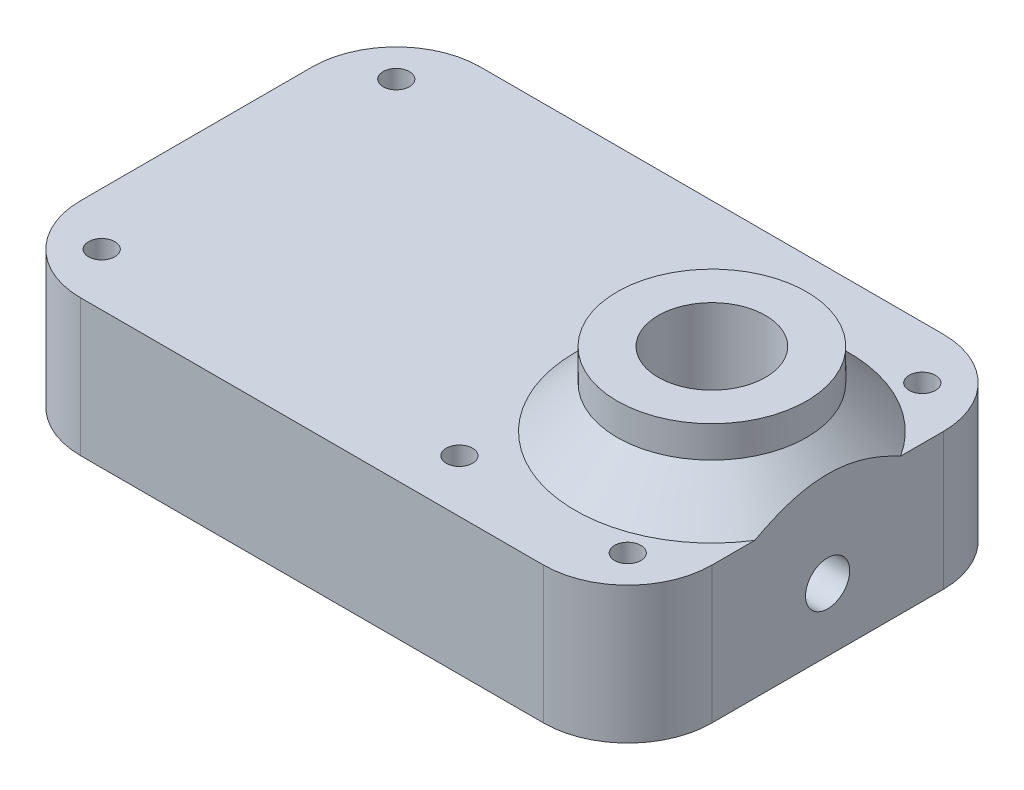
SolidWorks part; units mm, degrees
material "Aluminum 101"
ref_plane "Front Plane" through (0, 0, 0) normal (0, 0, 1) x (1, 0, 0)
ref_plane "Top Plane" through (0, 0, 0) normal (0, 1, 0) x (1, 0, 0)
ref_plane "Right Plane" through (0, 0, 0) normal (1, 0, 0) x (0, 0, -1)
sketch "Sketch1" plane through (0, 0, 0) normal (0, 1, 0) x (1, 0, 0)
  line L1 (-49, 19) -> (11, 19)
  line L2 (-49, 19) -> (-49, -19)
  line L3 (-49, -19) -> (11, -19)
  line L4 (11, 19) -> (11, -19)
  circle A1 centre (0, 0) radius 9
  point P8 (11, 0)
  dimension "D2" = 18
  dimension "D3" = 38
  dimension "D4" = 60
  dimension "D1" = 11
extrude "Base" add sketch "Sketch1" along normal blind 13 contours L4 A1 L1 L2 L3 | A1 region at (-21.387, 0, 0) region at (0, 0, 0)
fillet "AddALittleBeauty" radius 8 4 edges at (-49, 6.5, 19) (-49, 6.5, -19) (11, 6.5, -19) (11, 6.5, 19)
extrude "RodHolder" add sketch "Sketch1<3>" along normal blind 20 contours A1 region at (0, 0, 0)
sketch "Sketch1<3>" plane through (0, 0, 0) normal (0, 1, 0) x (1, 0, 0) same geometry as "Sketch1"
hole_wizard "M5x0.8 Tapped Hole for fixing rod" positions "Sketch3" profile "Sketch4" tap size "M5x0.8" standard "ANSI Metric"
sketch "Sketch3" plane through (11, 0, 0) normal (1, 0, 0) x (0, 0, -1)
  line L0 (11, 0) -> (-11, 0) construction
  point P0 (0, 6)
  dimension "D1" = 6
cosmetic thread "Hole Thread1" parameters "D1"=6.3524, "D2"=5
sketch "Sketch4" plane through (11, 6, 0) normal (0, 1, 0) x (0, 0, -1)
  line L0 (0, 0) -> (0, 11.6618)
  line L1 (0, 11.6618) -> (2.1, 10.4)
  line L2 (2.1, 10.4) -> (2.1, 0)
  line L5 (2.1, 0) -> (0, 0)
  line L10 (0, 11.6618) -> (-2.1, 10.4) construction
  line L11 (0, -6.35) -> (0, 107.95) construction
  dimension "Tap Drill Dia." = 4.2
  dimension "Tap Drill Depth" = 10.4
  dimension "Drill Angle" = 118
chamfer "Chamfer1" distance 4 angle 45 1 edges at (0, 13, 9)
hole_wizard "Ø10.2 (10.2) Rod Hole" positions "Sketch5" profile "Sketch6" hole size "Ø10.2" standard "ANSI Metric" end condition through all
sketch "Sketch5" plane through (0, 20, 0) normal (0, 1, 0) x (1, 0, 0)
  point P0 (0, 0)
sketch "Sketch6" plane through (0, 20, 0) normal (1, 0, 0) x (0, 0, 1)
  line L0 (0, 0) -> (0, 20)
  line L1 (0, 20) -> (5.1, 20)
  line L2 (5.1, 20) -> (5.1, 0)
  line L5 (5.1, 0) -> (0, 0)
  line L11 (0, -6.35) -> (0, 107.95) construction
  dimension "Thru Hole Dia." = 10.2
  dimension "Thru Hole Depth" = 20
hole_wizard "M3x0.5 Tapped Hole1" positions "Location" profile "Hole" tap size "M3x0.5" standard "ANSI Metric" end condition through all
sketch "Location" plane through (0, 0, 0) normal (0, -1, 0) x (-1, 0, 0)
  line L0 (41, 19) -> (-3, 19) construction
  line L2 (49, 11) -> (49, -11) construction
  line L4 (19, 18.3865) -> (19, -17.1189) construction
  line L5 (49, 0) -> (41.0253, 0) construction
  point P0 (-6, 14)
  point P3 (-6, -14)
  point P6 (44, -14)
  point P9 (44, 14)
  point P27 (10, 14)
  point P29 (10, -14)
  point P39 (19, 19)
  dimension "D1" = 28
  dimension "D3" = 25
  dimension "D2" = 25
  dimension "D4" = 16
sketch "Hole" plane through (6, 0, -14) normal (1, 0, 0) x (0, 0, -1)
  line L0 (0, 0) -> (0, 20)
  line L1 (0, 20) -> (1.25, 20)
  line L2 (1.25, 20) -> (1.25, 0.275)
  line L3 (1.25, 0.275) -> (1.525, 0)
  line L5 (1.525, 0) -> (0, 0)
  line L6 (-1.25, 0.275) -> (-1.525, 0) construction
  line L11 (0, -6.35) -> (0, 107.95) construction
  dimension "Thru Tap Drill Dia." = 2.5
  dimension "Thru Tap Drill Depth" = 20
  dimension "Near C'Sink Dia." = 3.05
  dimension "Near C'Sink Angle" = 90
cosmetic thread "Hole Thread2" parameters "D2"=3
cosmetic thread "Hole Thread3" parameters "D2"=3
cosmetic thread "Hole Thread4" parameters "D2"=3
cosmetic thread "Hole Thread5" parameters "D2"=3
cosmetic thread "Hole Thread6" parameters "D2"=3
cosmetic thread "Hole Thread7" parameters "D2"=3
sketch "Sketch9" plane through (0, 0, 0) normal (0, -1, 0) x (1, 0, 0)
  line L1 (-49, -11) -> (-49, 11) construction
  line L2 (-13.5, -13.5) -> (-40.5, -13.5)
  line L3 (-13.5, -13.5) -> (-13.5, 13.5)
  line L4 (-13.5, 13.5) -> (-40.5, 13.5)
  line L5 (-40.5, -13.5) -> (-40.5, 13.5)
  line L6 (-13.5, -13.5) -> (-40.5, 13.5) construction
  line L7 (-13.5, 13.5) -> (-40.5, -13.5) construction
  point P2 (-27, 0)
  dimension "D1" = 22
  dimension "D2" = 27
  dimension "D3" = 27
extrude "Cut-Extrude1" cut sketch "Sketch9" against normal blind 9
fillet "Fillet1" radius 2 8 edges at (-40.5, 4.5, -13.5) (-40.5, 4.5, 13.5) (-13.5, 4.5, 13.5) (-13.5, 4.5, -13.5) (-27, 9, 13.5) (-13.5, 9, 0) (-27, 9, -13.5) (-40.5, 9, 0)
equation "\"D2@Sketch1\"=10.00mm+8"
equation "\"D3@Sketch9\"=\"D2@Sketch9\""
equation "\"width\"= \"D3@Sketch1\""
equation "\"length\"= \"D4@Sketch1\""
equation "\"D1@Location\" = \"width\" - 10"
equation "\"D3@Location\"=(\"length\"-10)/2"
equation "\"D2@Location\"=(\"length\"-10)/2"
